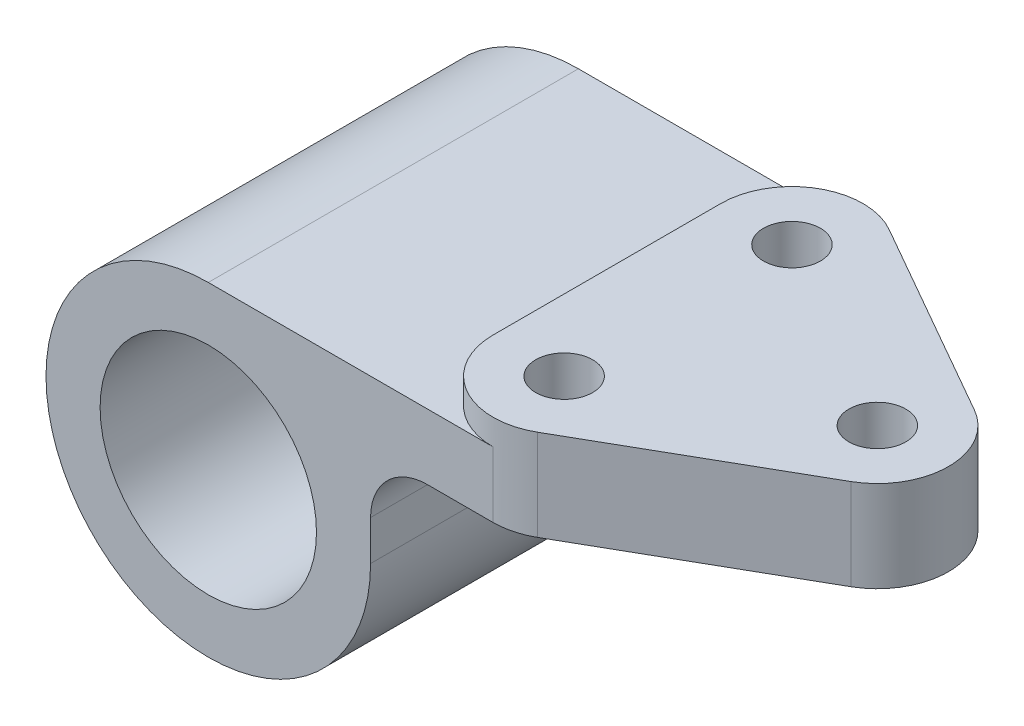
SolidWorks part; units mm, degrees
material "Plain Carbon Steel"
ref_plane "Front Plane" through (0, 0, 0) normal (0, 0, 1) x (1, 0, 0)
ref_plane "Top Plane" through (0, 0, 0) normal (0, 1, 0) x (1, 0, 0)
ref_plane "Right Plane" through (0, 0, 0) normal (1, 0, 0) x (0, 0, -1)
sketch "Sketch1" plane through (0, 0, 0) normal (0, 0, 1) x (1, 0, 0)
  line L0 (0, 28.5) -> (50, 28.5)
  line L1 (28.5, 0) -> (28.5, 7)
  line L2 (38.5, 17) -> (97.5, 17)
  line L3 (97.5, 17) -> (97.5, 33)
  line L4 (97.5, 33) -> (37.5, 33)
  line L5 (37.5, 33) -> (37.5, 28.5)
  circle A0 centre (0, 0) radius 19
  circle A1 centre (0, 0) radius 28.5
  arc A2 (28.5, 7) -> (38.5, 17) centre (38.5, 7) cw
  dimension "D1" = 38
  dimension "D2" = 57
  dimension "D3" = 10
  dimension "D4" = 33
  dimension "D5" = 16
  dimension "D6" = 50
  dimension "D7" = 60
  dimension "D8" = 12.5
extrude "Boss-Extrude1" add sketch "Sketch1" along normal mid plane 65 contours A1 A0 | L1 A2 L2 L3 L4 L5 L0 A1 region at (57.7582, 24.244, 0) region at (19.5825, 19.5825, 0)
sketch "Sketch2" plane through (0, 33, 0) normal (0, 1, 0) x (1, 0, 0)
  line L0 (37.5, -32.5) -> (37.5, 32.5) construction
  line L1 (37.5, -20) -> (37.5, 20)
  line L2 (56.2017, -30.853) -> (91.2017, -10.853)
  line L3 (56.2017, 30.853) -> (91.2017, 10.853)
  line L6 (97.5, 32.5) -> (37.5, 32.5) construction
  line L7 (97.5, -32.5) -> (37.5, -32.5) construction
  line L9 (37.5, 32.5) -> (97.5, 32.5)
  line L10 (37.5, 32.5) -> (37.5, -32.5)
  line L11 (37.5, -32.5) -> (97.5, -32.5)
  line L12 (97.5, 32.5) -> (97.5, -32.5)
  arc A0 (91.2017, 10.853) -> (91.2017, -10.853) centre (85, 0) cw
  arc A1 (37.5, -20) -> (56.2017, -30.853) centre (50, -20) ccw
  arc A2 (37.5, 20) -> (56.2017, 30.853) centre (50, 20) cw
  circle A3 centre (50, 20) radius 5
  circle A4 centre (50, -20) radius 5
  circle A5 centre (85, 0) radius 5
  line M9 (97.5, 32.5) -> (37.5, 32.5)
  line M10 (37.5, 32.5) -> (37.5, -32.5)
  line M11 (37.5, -32.5) -> (97.5, -32.5)
  line M12 (97.5, -32.5) -> (97.5, 32.5)
  dimension "D1" = 12.5
  dimension "D2" = 12.5
  dimension "D3" = 35
  dimension "D5" = 10
  dimension "D6" = 10
  dimension "D7" = 10
  dimension "D4" = 20
extrude "Cut-Extrude3" cut sketch "Sketch2" against normal up to next contours A2 L3 A0 L12 M9 | A1 L11 A0 L2 M12 | A5 | A3 | A4 region at (82.9257, 33, 23.8338) region at (82.9257, 33, -23.8338) region at (50, 33, -20) region at (50, 33, 20) region at (85, 33, 0)
extrude "Cut-Extrude4" cut sketch "Sketch2<4>" against normal blind 4.5 contours A1 M10 M11 | A2 L9 M10 region at (40.2921, 33, 29.7079) region at (40.2921, 33, -29.7079)
sketch "Sketch2<4>" plane through (0, 33, 0) normal (0, 1, 0) x (1, 0, 0) same geometry as "Sketch2"
